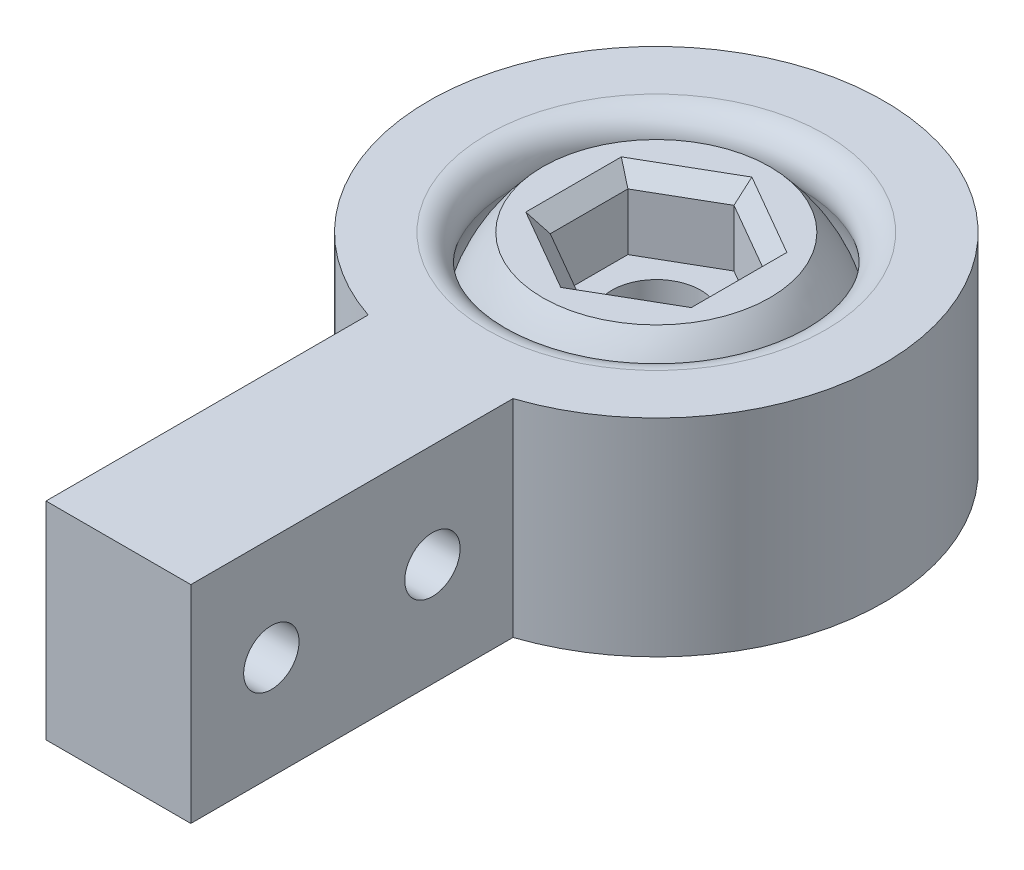
SolidWorks part; units mm, degrees
ref_plane "Front Plane" through (0, 0, 0) normal (0, 0, 1) x (1, 0, 0)
ref_plane "Top Plane" through (0, 0, 0) normal (0, 1, 0) x (1, 0, 0)
ref_plane "Right Plane" through (0, 0, 0) normal (1, 0, 0) x (0, 0, -1)
sketch "Sketch1" plane through (0, 0, 0) normal (0, 1, 0) x (1, 0, 0)
  circle A0 centre (0, 0) radius 4.2
  circle A1 centre (0, 0) radius 15.5
  circle A2 centre (0, 0) radius 25
  dimension "D1" = 8.4
  dimension "D2" = 31
  dimension "D3" = 50
extrude "Boss-Extrude1" add sketch "Sketch1" along normal mid plane 30 contours A2 A1 | A1 A0 region at (-15.0616, 0, 0) region at (-24.2929, 0, 0)
sketch "Sketch2" plane through (0, 0, 0) normal (0, 1, 0) x (1, 0, 0)
  line L0 (0, 15.5) -> (0, -15.5)
  arc A0 (0, -15.5) -> (0, 15.5) centre (0, 0) ccw
  dimension "D1" = 31
revolve "Cut-Revolve3" cut sketch "Sketch2" angle 360 about L0 region at (6.5784, 0, 0)
sketch "Sketch3" plane through (0, 15, 0) normal (0, 1, 0) x (1, 0, 0)
  circle A1 centre (0, 0) radius 25
  circle A2 centre (0, 0) radius 25
  dimension "D1" = 0
extrude "Cut-Extrude2" cut sketch "Sketch3" against normal blind 5
sketch "Sketch4" plane through (0, -15, 0) normal (0, -1, 0) x (1, 0, 0)
  circle A1 centre (0, 0) radius 25
  circle A2 centre (0, 0) radius 25
  dimension "D1" = 0
extrude "Cut-Extrude3" cut sketch "Sketch4" against normal blind 5
sketch "Sketch5" plane through (0, 0, 0) normal (0, 1, 0) x (1, 0, 0)
  line L0 (0, 14.85) -> (0, -14.85)
  arc A0 (0, -14.85) -> (0, 14.85) centre (0, 0) ccw
  dimension "D1" = 29.7
revolve "Revolve1" add sketch "Sketch5" angle 360 about L0 region at (6.3025, 0, 0)
sketch "Sketch6" plane through (0, 10, 0) normal (0, 1, 0) x (1, 0, 0)
  circle A0 centre (0, 0) radius 25
extrude "Cut-Extrude4" cut sketch "Sketch6" along normal blind 5
sketch "Sketch7" plane through (0, -10, 0) normal (0, -1, 0) x (1, 0, 0)
  circle A1 centre (0, 0) radius 25
  circle A2 centre (0, 0) radius 25
  dimension "D1" = 0
extrude "Cut-Extrude5" cut sketch "Sketch7" along normal blind 5
sketch "Sketch8" plane through (0, 10, 0) normal (0, 1, 0) x (1, 0, 0)
  circle A0 centre (0, 0) radius 4.2
  dimension "D1" = 8.4
extrude "Cut-Extrude6" cut sketch "Sketch8" against normal blind 23
sketch "Sketch9" plane through (0, 10, 0) normal (0, 1, 0) x (1, 0, 0)
  line L0 (0, -25) -> (0, -55)
  line L1 (-10, -25) -> (-10, -55)
  line L2 (10, -25) -> (10, -55)
  line L3 (-10, -55) -> (10, -55)
  line L4 (10, -25) -> (10, -20.3933)
  line L5 (10, -20.3933) -> (-10, -20.3933)
  line L6 (-10, -20.3933) -> (-10, -25)
  circle A0 centre (0, 0) radius 25 construction
  circle M3 centre (0, 0) radius 25
  dimension "D1" = 30
  dimension "D2" = 10
  dimension "D3" = 10
extrude "Boss-Extrude2" add sketch "Sketch9" against normal up to surface (20 mm away) contours L6 L1 L3 L0 M3 | L2 L4 L0 L3 M3 region at (5.0562, 10, 39.6519) region at (-5.0562, 10, 39.6519) up to face at (0, -10, -11.8427)
sketch "Sketch10" plane through (0, 10, 0) normal (0, 1, 0) x (1, 0, 0)
  line L6 (-7, -20.8567) -> (-7, -52)
  line L7 (-7, -52) -> (7, -52)
  line L8 (7, -52) -> (7, -20.8567)
  line L9 (-7, -20.8567) -> (-7, -52)
  line L10 (-7, -52) -> (7, -52)
  line L11 (7, -52) -> (7, -20.8567)
  line L12 (-10, -22.9129) -> (-10, -55)
  line L13 (-10, -55) -> (10, -55)
  line L14 (10, -55) -> (10, -22.9129)
  line L15 (-10, -22.9129) -> (-10, -55)
  line L16 (-10, -55) -> (10, -55)
  line L17 (10, -55) -> (10, -22.9129)
  arc A2 (7, -20.8567) -> (-7, -20.8567) centre (0, 0) ccw
  arc A3 (7, -20.8567) -> (-7, -20.8567) centre (0, 0) ccw
  arc A4 (10, -22.9129) -> (-10, -22.9129) centre (0, 0) ccw
  arc A5 (10, -22.9129) -> (-10, -22.9129) centre (0, 0) ccw
  dimension "D1" = 3
  dimension "D2" = 0
extrude "Cut-Extrude7" cut sketch "Sketch10" against normal blind 50
sketch "Sketch11" plane through (7, 0, 0) normal (1, 0, 0) x (0, 0, -1)
  line L0 (-52, 0) -> (-36.4283, 0)
  line L1 (-52, -10) -> (-52, 10) construction
  line L3 (-36.4283, 0) -> (-36.4283, 3.0153)
  circle A0 centre (-44.2142, 0) radius 2.675
  circle A1 centre (-28.6425, 0) radius 2.675
  dimension "D1" = 5.35
extrude "Cut-Extrude8" cut sketch "Sketch11" against normal through all both and the other way through all contours L0 A0 | L0 A0 | A1 region at (7, 1.1353, 44.2142) region at (7, -1.1353, 44.2142) region at (7, 0, 28.6425)
fillet "Fillet1" radius 2.5 2 edges at (0, -10, -11.8427) (0, 10, 11.8427)
sketch "Sketch12" plane through (0, 10, 0) normal (0, 1, 0) x (1, 0, 0)
  line L1 (0, 7.5056) -> (-6.5, 3.7528)
  line L2 (-6.5, 3.7528) -> (-6.5, -3.7528)
  line L3 (-6.5, -3.7528) -> (0, -7.5056)
  line L4 (0, -7.5056) -> (6.5, -3.7528)
  line L5 (6.5, -3.7528) -> (6.5, 3.7528)
  line L6 (6.5, 3.7528) -> (0, 7.5056)
  circle A0 centre (0, 0) radius 6.5 construction
  dimension "D1" = 13
extrude "Cut-Extrude9" cut sketch "Sketch12" against normal blind 7
sketch "Sketch13" plane through (0, -10, 0) normal (0, -1, 0) x (1, 0, 0)
  circle A1 centre (0, 0) radius 7.621
extrude "Cut-Extrude10" cut sketch "Sketch13" against normal blind 7
sketch "Sketch14" plane through (0, -3, 0) normal (0, -1, 0) x (1, 0, 0)
  circle A0 centre (0, 0) radius 4.3
  dimension "D1" = 8.6
extrude "Cut-Extrude11" cut sketch "Sketch14" along normal through all both and the other way through all
chamfer "Chamfer1" distance 1.5 angle 45 6 edges at (3.25, 10, 5.6292) (-3.25, 10, 5.6292) (-6.5, 10, 0) (-3.25, 10, -5.6292) (3.25, 10, -5.6292) (6.5, 10, 0)
